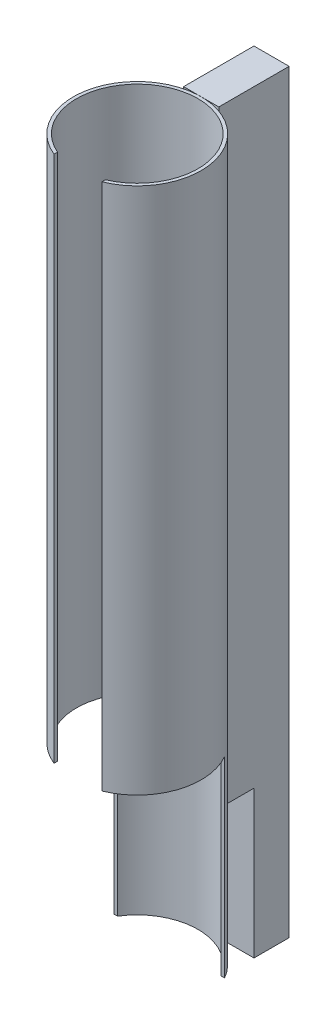
SolidWorks part; units mm, degrees
ref_plane "Plan de face" through (0, 0, 0) normal (0, 0, 1) x (1, 0, 0)
ref_plane "Plan de dessus" through (0, 0, 0) normal (0, 1, 0) x (1, 0, 0)
ref_plane "Plan de droite" through (0, 0, 0) normal (1, 0, 0) x (0, 0, -1)
sketch "Esquisse1" plane through (0, 0, 0) normal (0, 1, 0) x (1, 0, 0)
  circle A0 centre (0, 0) radius 40
  circle A1 centre (0, 0) radius 38
  dimension "D1" = 80
  dimension "D2" = 76
extrude "Boss.-Extru.1" add sketch "Esquisse1" along normal blind 450
sketch "Esquisse2" plane through (0, 0, 0) normal (0, 0, 1) x (1, 0, 0)
  line L0 (40, 0) -> (40, 450) construction
  line L1 (-40, 0) -> (40, 0)
  line L2 (-40, 0) -> (-40, 120)
  line L3 (-40, 120) -> (40, 120)
  line L4 (40, 0) -> (40, 120)
  dimension "D1" = 120
extrude "Enlèv. mat.-Extru.1" cut sketch "Esquisse2" along normal through all and the other way blind 20
sketch "Esquisse3" plane through (0, 0, 0) normal (1, 0, 0) x (0, 0, -1)
  line L0 (62, -22) -> (84, -22)
  line L1 (84, -22) -> (84, 450)
  line L2 (84, 450) -> (40, 450)
  line L3 (40, 450) -> (40, 70)
  line L4 (40, 0) -> (40, 450) construction
  line L5 (40, 70) -> (62, 70)
  line L6 (62, 70) -> (62, -22)
  dimension "D1" = 70
  dimension "D2" = 22
  dimension "D3" = 22
  dimension "D4" = 44
extrude "Boss.-Extru.2" add sketch "Esquisse3" along normal mid plane 22 separate body
sketch "Esquisse4" plane through (0, 0, 0) normal (0, 0, 1) x (1, 0, 0)
  line L1 (-15, 450) -> (15, 450)
  line L2 (-15, 450) -> (-15, 0)
  line L3 (-15, 0) -> (15, 0)
  line L4 (15, 450) -> (15, 0)
  line L5 (40, 450) -> (-40, 450) construction
  dimension "D1" = 30
extrude "Enlèv. mat.-Extru.2" cut sketch "Esquisse4" along normal through all
